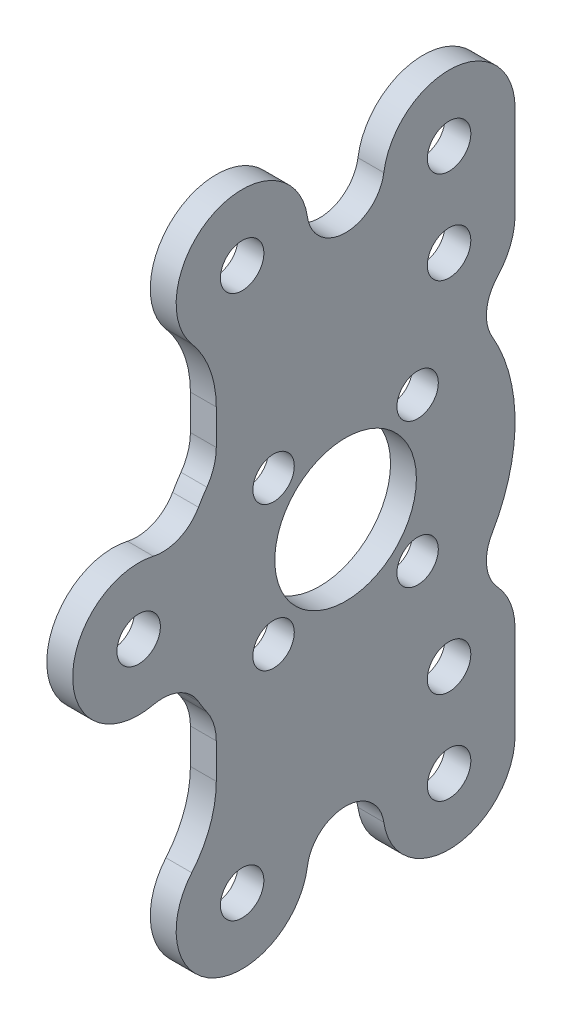
SolidWorks part; units mm, degrees
material "AR500"
ref_plane "Front Plane" through (0, 0, 0) normal (0, 0, 1) x (1, 0, 0)
ref_plane "Top Plane" through (0, 0, 0) normal (0, 1, 0) x (1, 0, 0)
ref_plane "Right Plane" through (0, 0, 0) normal (1, 0, 0) x (0, 0, -1)
ref_plane "Motor Front Plane" through (39.075, 0, 0) normal (1, 0, 0) x (0, 0, -1)
sketch "Sketch1" plane through (39.075, 0, 0) normal (1, 0, 0) x (0, 0, -1)
  line L1 (12.7, 21.997) -> (-25.4, 0) construction
  line L3 (12.7, 21.997) -> (12.7, -21.997) construction
  line L4 (-25.4, 0) -> (12.7, -21.997) construction
  line L5 (20.8, 21.997) -> (20.8, 32.6221) construction
  circle A0 centre (8.8388, -8.8388) radius 1.65 construction
  circle A1 centre (8.8388, 8.8388) radius 1.65 construction
  circle A2 centre (-8.8388, -8.8388) radius 1.65 construction
  circle A3 centre (-8.8388, 8.8388) radius 1.65 construction
  circle A4 centre (8.8388, -8.8388) radius 1.65 construction
  circle A5 centre (8.8388, 8.8388) radius 1.65 construction
  circle A6 centre (-8.8388, -8.8388) radius 1.65 construction
  circle A7 centre (-8.8388, 8.8388) radius 1.65 construction
  circle A8 centre (0, 0) radius 20.8 construction
  circle A9 centre (0, 0) radius 8.69
  circle A10 centre (-8.8388, 8.8388) radius 2.54
  circle A11 centre (8.8388, 8.8388) radius 2.54
  circle A12 centre (8.8388, -8.8388) radius 2.54
  circle A13 centre (-8.8388, -8.8388) radius 2.54
  circle A14 centre (-8.8388, 8.8388) radius 3.81 construction
  circle A16 centre (12.7, 21.997) radius 2.667
  circle A18 centre (12.7, -21.997) radius 2.667
  circle A19 centre (-25.4, 0) radius 2.667
  arc A20 (-19.925, -5.9695) -> (4.7928, -20.2403) centre (0, 0) ccw
  arc A21 (-19.925, 5.9695) -> (4.7928, 20.2403) centre (0, 0) cw
  arc A23 (15.1322, 14.2708) -> (15.1322, -14.2708) centre (0, 0) cw
  arc A24 (-19.925, -5.9695) -> (-19.925, 5.9695) centre (-25.4, 0) cw
  arc A25 (4.7928, 20.2403) -> (15.1322, 14.2708) centre (12.7, 21.997) cw
  arc A27 (4.7928, -20.2403) -> (15.1322, -14.2708) centre (12.7, -21.997) ccw
  circle A28 centre (0, 0) radius 25.4 construction
  point P25 (0, 0)
  point P27 (0, 0)
  point P28 (0, 0)
  point P30 (0, 0)
  point P39 (0, 0)
  point P40 (0, 0)
  dimension "D1" = 41.6
  dimension "D2" = 5.08
  dimension "D3" = 7.62
  dimension "D4" = 5.334
  dimension "D5" = 50.8
extrude "Boss-Extrude1" add sketch "Sketch1" along normal blind 3.175
fillet "Fillet1" radius 5.08 6 edges at (40.6625, 5.9695, 19.925) (40.6625, -14.2708, -15.1322) (40.6625, -20.2403, -4.7928) (40.6625, -5.9695, 19.925) (40.6625, 20.2403, -4.7928) (40.6625, 14.2708, -15.1322)
sketch "Sketch2" plane through (42.25, 0, 0) normal (1, 0, 0) x (0, 0, -1)
  line L0 (-12.7, -33.3375) -> (-12.7, 33.3375) construction
  line L5 (0, 0) -> (-12.7, 0) construction
  line L6 (0, 0) -> (0, 30.48) construction
  line L11 (12.7, 33.3375) -> (12.7, 21.997) construction
  line L13 (20.8, 33.3375) -> (20.8, 21.997)
  line L14 (-15.875, 19.8978) -> (-15.875, 13.4397)
  line L15 (11.7095, 24.4733) -> (-15.875, 13.4397)
  arc A24 (-4.6874, 34.5243) -> (-18.8821, 28.1038) centre (-12.7, 33.3375) ccw
  circle A27 centre (-12.7, 33.3375) radius 2.667
  circle A32 centre (12.7, 33.3375) radius 2.667
  arc A33 (4.6874, 34.5243) -> (20.8, 33.3375) centre (12.7, 33.3375) cw
  circle A34 centre (-25.4, 0) radius 2.667 construction
  arc A35 (-4.6874, 34.5243) -> (4.6874, 34.5243) centre (0, 35.2185) ccw
  arc A39 (18.6368, 16.4866) -> (4.9595, 24.3833) centre (12.7, 21.997) ccw construction
  arc A40 (-18.8821, 28.1038) -> (-15.875, 19.8978) centre (-28.575, 19.8978) cw
  arc A41 (0.0843, 20.7998) -> (-18.0553, 10.3269) centre (0, 0) ccw construction
  arc A42 (20.8, 21.997) -> (11.7095, 24.4733) centre (14.614, 17.2119) ccw
  circle A43 centre (12.7, 21.997) radius 2.667 construction
  point P29 (0, 0)
  dimension "D3" = 30.48
  dimension "D1" = 6.35
  dimension "D4" = 12.7
  dimension "D2" = 66.675
extrude "Boss-Extrude2" add sketch "Sketch2" against normal up to surface (3.175 mm away) up to face at (39.075, -21.997, -15.367)
mirror "Mirror1" about plane through (0, 0, 0) normal (0, 1, 0) of "Boss-Extrude2"
fillet "Fillet2" radius 6.35 2 edges at (40.6625, -13.4397, 15.875) (40.6625, 13.4397, 15.875)
equation "\"D1@Sketch1\"=41.6mm"
